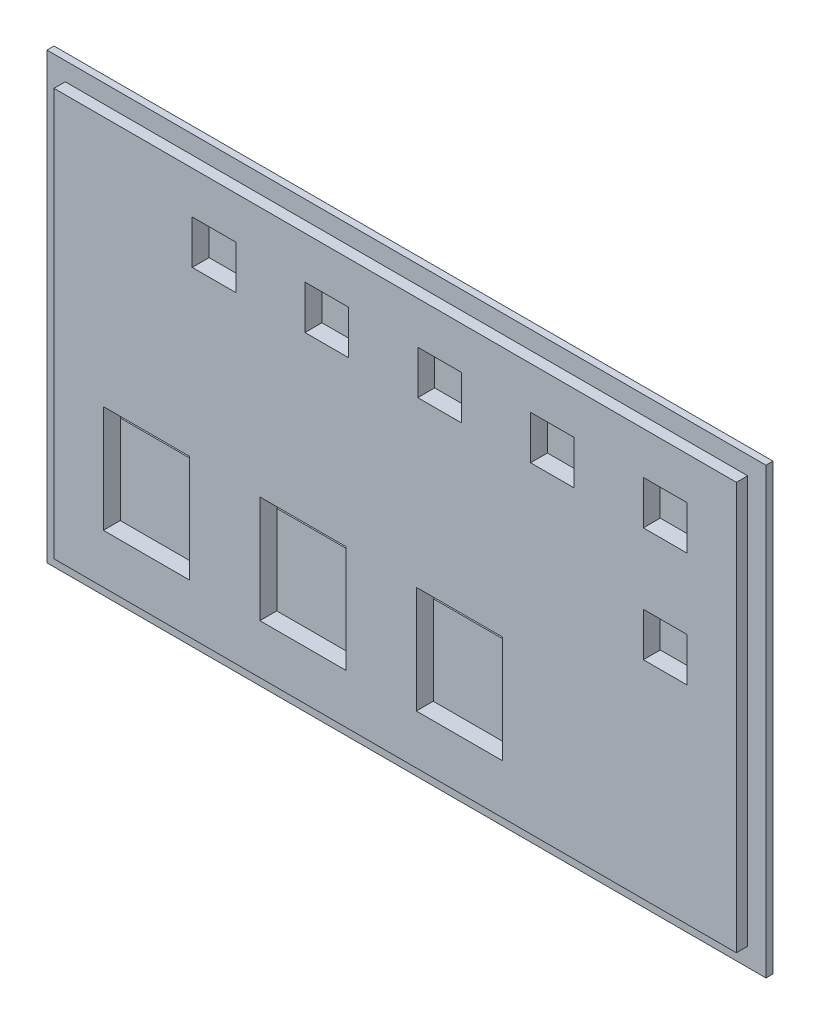
SolidWorks part; units mm, degrees
ref_plane "Přední rovina" through (0, 0, 0) normal (0, 0, 1) x (1, 0, 0)
ref_plane "Horní rovina" through (0, 0, 0) normal (0, 1, 0) x (1, 0, 0)
ref_plane "Pravá rovina" through (0, 0, 0) normal (1, 0, 0) x (0, 0, -1)
sketch "Skica1" plane through (0, 0, 0) normal (0, 0, 1) x (1, 0, 0)
  line L0 (9.6, 22.2) -> (21.8, 22.2)
  line L1 (0, 0) -> (102, 0)
  line L2 (0, 0) -> (0, 63)
  line L3 (0, 63) -> (102, 63)
  line L4 (102, 0) -> (102, 63)
  line L25 (22.2, 54.4) -> (28.4, 54.4)
  line L26 (22.2, 54.4) -> (22.2, 48.2)
  line L27 (22.2, 48.2) -> (28.4, 48.2)
  line L28 (28.4, 54.4) -> (28.4, 48.2)
  line L29 (38.2, 54.4) -> (44.4, 54.4)
  line L30 (38.2, 54.4) -> (38.2, 48.2)
  line L31 (38.2, 48.2) -> (44.4, 48.2)
  line L32 (44.4, 54.4) -> (44.4, 48.2)
  line L33 (54.2, 54.4) -> (60.4, 54.4)
  line L34 (54.2, 54.4) -> (54.2, 48.2)
  line L35 (54.2, 48.2) -> (60.4, 48.2)
  line L36 (60.4, 54.4) -> (60.4, 48.2)
  line L37 (70.2, 54.4) -> (76.4, 54.4)
  line L38 (70.2, 54.4) -> (70.2, 48.2)
  line L39 (70.2, 48.2) -> (76.4, 48.2)
  line L40 (76.4, 54.4) -> (76.4, 48.2)
  line L41 (86.2, 54.4) -> (92.4, 54.4)
  line L42 (86.2, 54.4) -> (86.2, 48.2)
  line L43 (86.2, 48.2) -> (92.4, 48.2)
  line L44 (92.4, 54.4) -> (92.4, 48.2)
  line L45 (2.6, 60.4) -> (99.4, 60.4)
  line L46 (2.6, 60.4) -> (2.6, 2.6)
  line L47 (2.6, 2.6) -> (99.4, 2.6)
  line L48 (99.4, 60.4) -> (99.4, 2.6)
  line L49 (9.6, 24.8) -> (21.8, 24.8)
  line L50 (9.6, 24.8) -> (9.6, 9.6)
  line L51 (9.6, 9.6) -> (21.8, 9.6)
  line L52 (21.8, 24.8) -> (21.8, 9.6)
  line L53 (31.8, 24.8) -> (44, 24.8)
  line L54 (31.8, 24.8) -> (31.8, 9.6)
  line L55 (31.8, 9.6) -> (44, 9.6)
  line L56 (44, 24.8) -> (44, 9.6)
  line L57 (54, 24.8) -> (66.2, 24.8)
  line L58 (54, 24.8) -> (54, 9.6)
  line L59 (54, 9.6) -> (66.2, 9.6)
  line L60 (66.2, 24.8) -> (66.2, 9.6)
  line L62 (31.8, 22.2) -> (44, 22.2)
  line L63 (86.2, 38.2) -> (92.4, 38.2)
  line L64 (54, 22.2) -> (66.2, 22.2)
  line L65 (86.2, 38.2) -> (86.2, 32)
  line L66 (86.2, 32) -> (92.4, 32)
  line L67 (92.4, 38.2) -> (92.4, 32)
  point P29 (89.3, 54.4)
  dimension "D2" = 6.2
  dimension "D3" = 6.2
  dimension "D4" = 7
  dimension "D5" = 6
  dimension "D6" = 6.2
  dimension "D7" = 6.2
  dimension "D8" = 6.2
  dimension "D9" = 6.2
  dimension "D10" = 6.2
  dimension "D11" = 6.2
  dimension "D12" = 6.2
  dimension "D13" = 6.2
  dimension "D14" = 9.8
  dimension "D15" = 102
  dimension "D16" = 9.8
  dimension "D17" = 9.8
  dimension "D18" = 63
  dimension "D19" = 9.8
  dimension "D20" = 2.6
  dimension "D21" = 2.6
  dimension "D22" = 2.6
  dimension "D23" = 2.6
  dimension "D24" = 6
  dimension "D25" = 12.2
  dimension "D26" = 15.2
  dimension "D27" = 12.2
  dimension "D28" = 12.2
  dimension "D29" = 2.6
  dimension "D30" = 2.6
  dimension "D31" = 2.6
  dimension "D32" = 7
  dimension "D33" = 7
  dimension "D34" = 10
  dimension "D35" = 10
  dimension "D36" = 6.2
  dimension "D37" = 6.2
  dimension "D38" = 10
  dimension "D39" = 96.8
extrude "Přidat vysunutím1" add sketch "Skica1" along normal blind 2.6 contours L48 L45 L46 L47 L25 L28 L27 L26 L29 L32 L31 L30 L33 L36 L35 L34 L37 L40 L39 L38 L41 L44 L43 L42 L49 L52 L51 L50 L53 L56 L55 L54 L57 L60 L59 L58 region at (51.9577, 32.3343, 0)
extrude "Přidat vysunutím2" add sketch "Skica1<3>" along normal blind 1 contours L1 L4 L3 L2 L45 L48 L47 L46 region at (1.1989, 31.5, 0)
sketch "Skica1<3>" plane through (0, 0, 0) normal (0, 0, 1) x (1, 0, 0) same geometry as "Skica1"
extrude "Přidat vysunutím3" add sketch "Skica1<5>" along normal blind 0.2 contours L64 L58 L59 L60 | L62 L54 L55 L56 | L52 L0 L50 L51 | L67 L63 L65 L66 | L44 L41 L42 L43 | L40 L37 L38 L39 | L36 L33 L34 L35 | L32 L29 L30 L31 | L28 L25 L26 L27 region at (15.7, 15.9, 0) region at (25.3, 51.3, 0) region at (41.3, 51.3, 0) region at (57.3, 51.3, 0) region at (73.3, 51.3, 0) region at (89.3, 51.3, 0) region at (37.9, 15.9, 0) region at (60.1, 15.9, 0) region at (89.3, 35.1, 0)
sketch "Skica1<5>" plane through (0, 0, 0) normal (0, 0, 1) x (1, 0, 0) same geometry as "Skica1"
